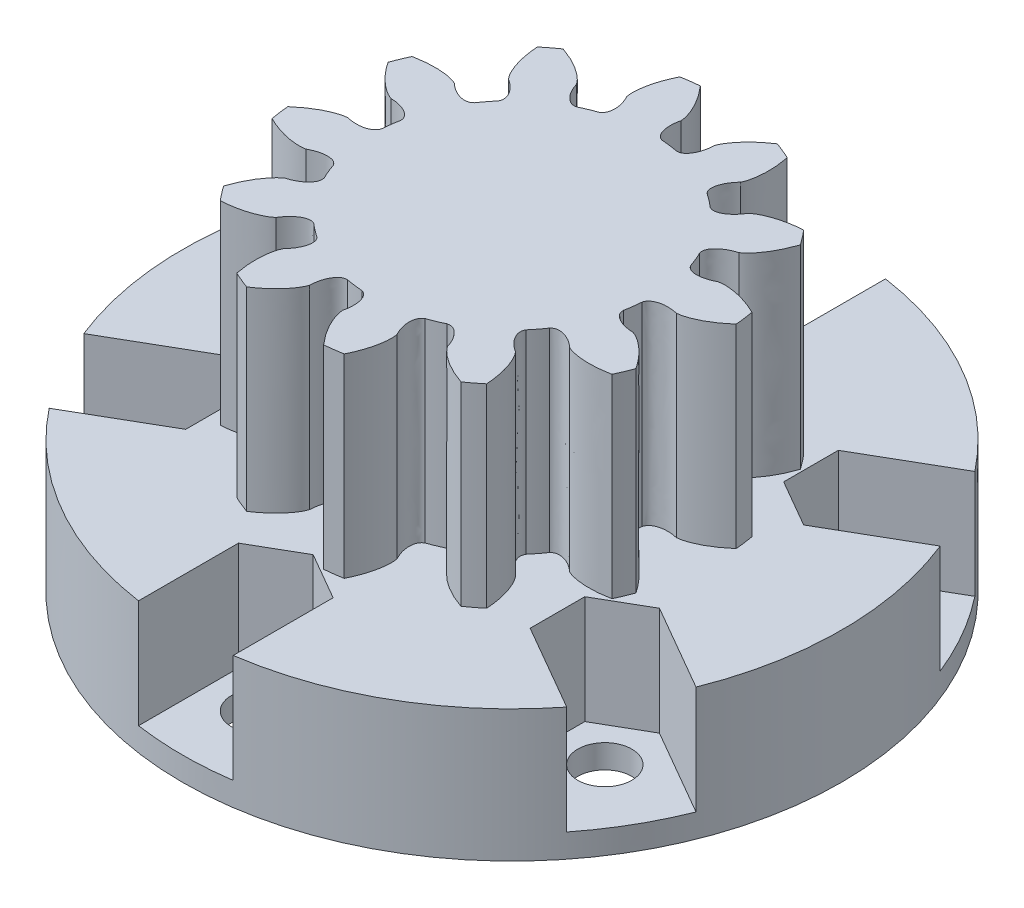
SolidWorks part; units mm, degrees
ref_plane "Front Plane" through (0, 0, 0) normal (0, 0, 1) x (1, 0, 0)
ref_plane "Top Plane" through (0, 0, 0) normal (0, 1, 0) x (1, 0, 0)
ref_plane "Right Plane" through (0, 0, 0) normal (1, 0, 0) x (0, 0, -1)
sketch "Sketch6" plane through (0, 0, 0) normal (0, 1, 0) x (1, 0, 0)
  circle A0 centre (0, 0) radius 19.5
  dimension "D1" = 39
extrude "Boss-Extrude1" add sketch "Sketch6" along normal blind 7.8 separate body
sketch "Sketch7" plane through (0, 7.8, 0) normal (0, 1, 0) x (1, 0, 0)
  circle A0 centre (0, 0) radius 10.5
  circle A1 centre (0, 0) radius 12.25
  circle A2 centre (0, 0) radius 8.3125
  dimension "D1" = 21
  dimension "D2" = 24.5
  dimension "D3" = 16.625
sketch "Sketch8" plane through (0, 0, 0) normal (0, 1, 0) x (1, 0, 0)
  line L0 (16.2938, 10.5) -> (-16.2938, 10.5) construction
  line L1 (-13.5138, 5.5814) -> (13.5138, 15.4186) construction
  line L2 (0, 0) -> (0, 15.4026) construction
  line L3 (0, 0) -> (-3.3746, 9.2717) construction
  line L4 (-3.3746, 9.2717) -> (0, 10.5)
  arc A0 (-3.3746, 9.2717) -> (0.1471, 9.8657) centre (0, 0) cw
  circle A1 centre (0, 0) radius 10.5 construction
  circle A2 centre (0, 0) radius 9.8668 construction
  point P3 (0, 10.5)
  point P9 (0, 10.5)
  dimension "D1" = 20
sketch "Sketch10" plane through (0, 0, 0) normal (0, 1, 0) x (1, 0, 0)
  line L0 (-3.3746, 9.2717) -> (0, 10.5)
  line L1 (-4.1825, 8.9364) -> (-0.1374, 10.8297) construction
  line L2 (-4.9575, 8.5309) -> (-0.3395, 11.2146) construction
  line L3 (-5.6936, 8.0583) -> (-0.6168, 11.6453) construction
  line L4 (-6.3849, 7.5224) -> (-0.9786, 12.1112) construction
  line L5 (-7.026, 6.9273) -> (-1.4331, 12.6) construction
  line L6 (-7.612, 6.2778) -> (-1.9866, 13.0986) construction
  line L7 (-1.6409, 9.7294) -> (0.1297, 10.028) construction
  arc A0 (-3.3746, 9.2717) -> (-4.1825, 8.9364) centre (0, 0) ccw
  circle A1 centre (0, 0) radius 9.8668 construction
  arc A2 (-4.1825, 8.9364) -> (-4.9575, 8.5309) centre (0, 0) ccw
  arc A3 (-4.9575, 8.5309) -> (-5.6936, 8.0583) centre (0, 0) ccw
  arc A4 (-5.6936, 8.0583) -> (-6.3849, 7.5224) centre (0, 0) ccw
  arc A5 (-6.3849, 7.5224) -> (-7.026, 6.9273) centre (0, 0) ccw
  arc A6 (-7.026, 6.9273) -> (-7.612, 6.2778) centre (0, 0) ccw
  arc A7 (-3.3746, 9.2717) -> (-1.6409, 9.7294) centre (0, 0) cw
  arc A8 (-1.6409, 9.7294) -> (0.1471, 9.8657) centre (0, 0) cw
  arc A9 (0.1471, 9.8657) -> (-3.3746, 9.2717) centre (0, 0) ccw construction
  dimension "D1" = 3.5912
  dimension "D3" = 4.4662
  dimension "D4" = 5.3412
  dimension "D5" = 6.2162
  dimension "D6" = 7.0912
  dimension "D7" = 7.9662
  dimension "D8" = 8.8412
  dimension "D10" = 1.7956
  dimension "D2" = 0.875
  dimension "D9" = 1.7956
sketch "Sketch15" plane through (0, 0, 0) normal (0, 1, 0) x (1, 0, 0)
  line L0 (-8.3796, 8.9356) -> (9.5703, 7.6467) construction
  line L1 (-3.3746, 9.2717) -> (0, 10.5) construction
  line L2 (-3.3746, 9.2717) -> (0, 10.5) construction
  line L3 (0.1471, 9.8657) -> (0.5954, 8.2912) construction
  line L4 (-6.7576, 10.2175) -> (10.7199, 5.9284) construction
  line L5 (0.1471, 9.8657) -> (0.2972, 8.4862) construction
  line L6 (-5.566, 10.9125) -> (11.3185, 4.6856) construction
  line L7 (0.1471, 9.8657) -> (0.1425, 8.8072) construction
  line L8 (-3.7093, 11.6749) -> (11.9317, 2.7744) construction
  line L9 (0.1471, 9.8657) -> (0.0874, 9.5144) construction
  line L10 (-4.577, 11.3628) -> (11.6892, 3.6641) construction
  line L11 (0.1471, 9.8657) -> (0.0811, 9.1582) construction
  line L12 (0.0874, 9.5144) -> (0.0811, 9.1582) construction
  line L13 (0.0811, 9.1582) -> (0.1425, 8.8072) construction
  line L14 (0.1425, 8.8072) -> (0.2972, 8.4862) construction
  line L15 (0.2972, 8.4862) -> (0.5954, 8.2912) construction
  circle A0 centre (0, 0) radius 12.25 construction
  arc A1 (-3.3746, 9.2717) -> (0.1471, 9.8657) centre (0, 0) cw construction
  circle A2 centre (0, 0) radius 8.3125 construction
  circle A3 centre (0, 0) radius 8.3125 construction
  dimension "D1" = 70
  dimension "D2" = 70
  dimension "D3" = 70
  dimension "D4" = 70
  dimension "D5" = 70
sketch "Sketch11" plane through (0, 7.8, 0) normal (0, 1, 0) x (1, 0, 0)
  line L1 (0, 0) -> (1.4144, 10.7435) construction
  line L2 (0, -9.8668) -> (0, -10.5) construction
  line L3 (0, -10.5) -> (0, -11.1332) construction
  line L5 (0, 0) -> (0, 11.9235) construction
  circle A1 centre (0, 0) radius 9.8668 construction
  circle A2 centre (0, 0) radius 10.5 construction
  arc A4 (0.5954, 8.2912) -> (1.5708, 8.1627) centre (0, 0) cw
  arc A5 (-1.9866, 13.0986) -> (5.3091, 12.1381) centre (0, 0) cw
  spline S0 degree 3 poles (-1.9866, 13.0986) (-1.6236, 12.7989) (-1.1413, 12.333) (-0.6251, 11.6711) (-0.3466, 11.2404) (-0.1429, 10.8555) (0.0426, 10.4112) (0.1353, 10.0836) (0.1471, 9.8657) knots 0 0 0 0 0.356747 0.505732 0.635125 0.744926 0.835134 1 1 1 1
  spline S1 degree 3 poles (2.4114, 9.5676) (2.4046, 9.3312) (2.3515, 8.9715) (2.1063, 8.43) (1.8374, 8.1563) (1.5708, 8.1627) knots 0 0 0 0 0.4 0.6 1 1 1 1
  spline S2 degree 3 poles (0.1471, 9.8657) (0.0924, 9.6356) (0.0506, 9.2744) (0.1474, 8.6879) (0.3362, 8.3539) (0.5954, 8.2912) knots 0 0 0 0 0.4 0.6 1 1 1 1
  spline S3 degree 3 poles (5.3091, 12.1381) (4.8809, 11.9426) (4.2944, 11.6174) (3.6245, 11.1117) (3.2441, 10.7677) (2.9477, 10.4486) (2.6535, 10.0675) (2.4791, 9.775) (2.4114, 9.5676) knots 0 0 0 0 0.356747 0.505732 0.635125 0.744926 0.835134 1 1 1 1
  dimension "D1" = 7.5
extrude "Boss-Extrude2" add sketch "Sketch7" along normal blind 11.5 contours A1
extrude "Cut-Extrude1" cut sketch "Sketch11" along normal up to surface (11.5 mm away) up to face at (0, 19.3, 12.25)
pattern_circular "CirPattern1" count 12 over 360 about axis through (0, 19.3, 0) along (0, -1, 0) of "Cut-Extrude1"
sketch "Sketch16" plane through (0, 7.8, 0) normal (0, 1, 0) x (1, 0, 0)
  line L6 (2.8, 16.6166) -> (2.8, 19.2979)
  line L7 (0, 18.2332) -> (-2.8, 16.6166) construction
  line L8 (-2.8, 16.6166) -> (-2.8, 13.3834)
  line L9 (-2.8, 13.3834) -> (0, 11.7668)
  line L10 (0, 11.7668) -> (2.8, 13.3834)
  line L11 (2.8, 13.3834) -> (2.8, 16.6166)
  line L12 (2.8, 16.6166) -> (0, 18.2332) construction
  line L13 (15.7904, 5.8834) -> (18.1125, 7.2241)
  line L14 (12.9904, 10.7332) -> (10.1904, 9.1166)
  line L15 (-2.8, 16.6166) -> (-2.8, 19.2979)
  line L16 (10.1904, 9.1166) -> (10.1904, 5.8834)
  line L17 (10.1904, 5.8834) -> (12.9904, 4.2668)
  line L18 (12.9904, 4.2668) -> (15.7904, 5.8834)
  line L19 (12.9904, 10.7332) -> (15.3125, 12.0738)
  line L20 (15.7904, 9.1166) -> (12.9904, 10.7332) construction
  line L21 (15.7904, 5.8834) -> (15.7904, 9.1166) construction
  line L22 (12.9904, -10.7332) -> (15.3125, -12.0738)
  line L23 (15.7904, -5.8834) -> (12.9904, -4.2668)
  line L24 (12.9904, -4.2668) -> (10.1904, -5.8834)
  line L25 (10.1904, -5.8834) -> (10.1904, -9.1166)
  line L26 (10.1904, -9.1166) -> (12.9904, -10.7332)
  line L27 (15.7904, -5.8834) -> (18.1125, -7.2241)
  line L28 (15.7904, -9.1166) -> (15.7904, -5.8834) construction
  line L29 (12.9904, -10.7332) -> (15.7904, -9.1166) construction
  line L30 (-2.8, -16.6166) -> (-2.8, -19.2979)
  line L31 (2.8, -16.6166) -> (2.8, -13.3834)
  line L32 (2.8, -13.3834) -> (0, -11.7668)
  line L33 (0, -11.7668) -> (-2.8, -13.3834)
  line L34 (-2.8, -13.3834) -> (-2.8, -16.6166)
  line L35 (2.8, -16.6166) -> (2.8, -19.2979)
  line L36 (0, -18.2332) -> (2.8, -16.6166) construction
  line L37 (-2.8, -16.6166) -> (0, -18.2332) construction
  line L38 (-15.7904, -5.8834) -> (-18.1125, -7.2241)
  line L39 (-12.9904, -10.7332) -> (-10.1904, -9.1166)
  line L40 (-10.1904, -9.1166) -> (-10.1904, -5.8834)
  line L41 (-10.1904, -5.8834) -> (-12.9904, -4.2668)
  line L42 (-12.9904, -4.2668) -> (-15.7904, -5.8834)
  line L43 (-12.9904, -10.7332) -> (-15.3125, -12.0738)
  line L44 (-15.7904, -9.1166) -> (-12.9904, -10.7332) construction
  line L45 (-15.7904, -5.8834) -> (-15.7904, -9.1166) construction
  line L46 (-12.9904, 10.7332) -> (-15.3125, 12.0738)
  line L47 (-15.7904, 5.8834) -> (-12.9904, 4.2668)
  line L48 (-12.9904, 4.2668) -> (-10.1904, 5.8834)
  line L49 (-10.1904, 5.8834) -> (-10.1904, 9.1166)
  line L50 (-10.1904, 9.1166) -> (-12.9904, 10.7332)
  line L51 (-15.7904, 5.8834) -> (-18.1125, 7.2241)
  line L52 (-15.7904, 9.1166) -> (-15.7904, 5.8834) construction
  line L53 (-12.9904, 10.7332) -> (-15.7904, 9.1166) construction
  circle A0 centre (0, 15) radius 1.6
  circle A2 centre (0, 0) radius 19.5 construction
  arc A3 (2.8, 19.2979) -> (-2.8, 19.2979) centre (0, 0) ccw
  circle A10 centre (0, 15) radius 2.8 construction
  circle A11 centre (12.9904, 7.5) radius 1.6
  arc A12 (18.1125, 7.2241) -> (15.3125, 12.0738) centre (0, 0) ccw
  circle A13 centre (12.9904, 7.5) radius 2.8 construction
  circle A14 centre (12.9904, -7.5) radius 1.6
  arc A15 (15.3125, -12.0738) -> (18.1125, -7.2241) centre (0, 0) ccw
  circle A16 centre (12.9904, -7.5) radius 2.8 construction
  circle A17 centre (0, -15) radius 1.6
  arc A18 (-2.8, -19.2979) -> (2.8, -19.2979) centre (0, 0) ccw
  circle A19 centre (0, -15) radius 2.8 construction
  circle A20 centre (-12.9904, -7.5) radius 1.6
  arc A21 (-18.1125, -7.2241) -> (-15.3125, -12.0738) centre (0, 0) ccw
  circle A22 centre (-12.9904, -7.5) radius 2.8 construction
  circle A23 centre (-12.9904, 7.5) radius 1.6
  arc A24 (-15.3125, 12.0738) -> (-18.1125, 7.2241) centre (0, 0) ccw
  circle A25 centre (-12.9904, 7.5) radius 2.8 construction
  point P24 (0, 0)
  point P39 (0, 0)
  dimension "D2" = 3.2
  dimension "D3" = 6
  dimension "D5" = 5.6
  dimension "D1" = 15
extrude "Cut-Extrude2" cut sketch "Sketch16" against normal blind 6.4
extrude "Cut-Extrude3" cut sketch "Sketch16<3>" against normal through all contours A0 | A14 | A11 | A23 | A20 | A17 region at (0, 7.8, -15) region at (12.9904, 7.8, -7.5) region at (12.9904, 7.8, 7.5)
sketch "Sketch16<3>" plane through (0, 7.8, 0) normal (0, 1, 0) x (1, 0, 0) same geometry as "Sketch16"
equation "\"D1@Sketch7\"=\"Module@Drive Module.Assembly\"*\"Sun Teeth Num@Drive Module.Assembly\""
equation "\"D2@Sketch10\"=\"Module@Drive Module.Assembly\"*.5"
equation "\"D3@Sketch10\"=\"D1@Sketch10\"+\"D2@Sketch10\""
equation "\"D4@Sketch10\"=\"D3@Sketch10\"+\"D2@Sketch10\""
equation "\"D5@Sketch10\"=\"D4@Sketch10\"+\"D2@Sketch10\""
equation "\"D6@Sketch10\"=\"D5@Sketch10\"+\"D2@Sketch10\""
equation "\"D7@Sketch10\"=\"D6@Sketch10\"+\"D2@Sketch10\""
equation "\"D8@Sketch10\"=\"D7@Sketch10\"+\"D2@Sketch10\""
equation "\"D2@Sketch7\"=\"D1@Sketch7\"+2*\"Addendum@Drive Module.Assembly\""
equation "\"D3@Sketch7\"=\"D1@Sketch7\"-2*\"Dedendum@Drive Module.Assembly\""
equation "\"D1@Sketch15\"=90-\"Pressure Angle@Drive Module.Assembly\""
equation "\"D2@Sketch15\"=\"D1@Sketch15\""
equation "\"D3@Sketch15\"=\"D1@Sketch15\""
equation "\"D4@Sketch15\"=\"D1@Sketch15\""
equation "\"D5@Sketch15\"=\"D4@Sketch15\""
equation "\"D1@CirPattern1\"=\"Sun Teeth Num@Drive Module.Assembly\""
equation "\"D10@Sketch10\"=\"D1@Sketch10\"-\"D9@Sketch10\""
equation "\"D1@Sketch11\"=90/\"Sun Teeth Num@Drive Module.Assembly\""
equation "\"D1@Sketch6\"=  39"
equation "\"D1@Boss-Extrude2\"=\"Gear Thickness@Drive Module.Assembly\"-3.5"
